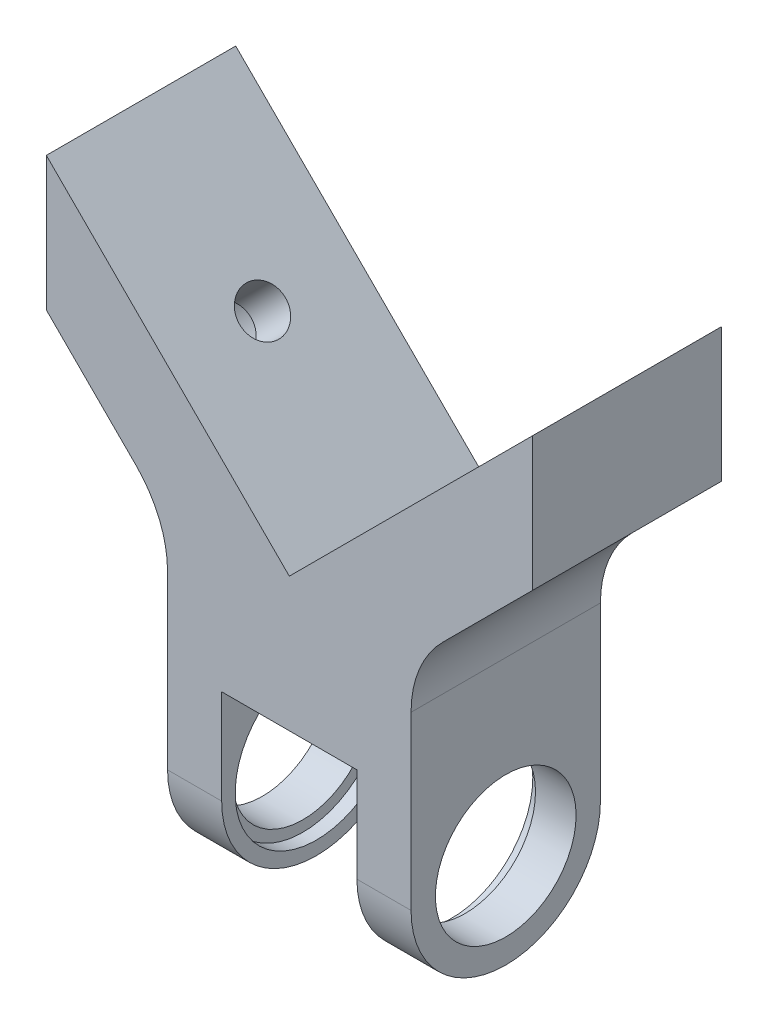
SolidWorks part; units mm, degrees
ref_plane "Alzado" through (0, 0, 0) normal (0, 0, 1) x (1, 0, 0)
ref_plane "Planta" through (0, 0, 0) normal (0, 1, 0) x (1, 0, 0)
ref_plane "Vista lateral" through (0, 0, 0) normal (1, 0, 0) x (0, 0, -1)
sketch "Croquis1" plane through (0, 0, 0) normal (1, 0, 0) x (0, 0, -1)
  line L0 (-7, 0) -> (-7, 7)
  line L1 (-7, 7) -> (7, 7)
  line L2 (7, 7) -> (7, 0)
  circle A0 centre (0, 0) radius 5.2
  circle A1 centre (0, 0) radius 6
  circle A2 centre (0, 0) radius 7
  dimension "D1" = 10.4
  dimension "D2" = 12
  dimension "D3" = 14
extrude "Saliente-Extruir1" add sketch "Croquis1" against normal blind 3 from offset 9 contours A1 A0 region at (0, 0, 5.8303)
extrude "Saliente-Extruir2" add sketch "Croquis1<3>" against normal blind 4 from offset 9 contours A2 L1 L0 | A2 L2 L1 | A2 A1 region at (0, 4.8097, 4.8097) region at (0, 5.4364, 5.4364) region at (0, 5.4364, -5.4364)
sketch "Croquis1<3>" plane through (0, 0, 0) normal (1, 0, 0) x (0, 0, -1) same geometry as "Croquis1"
extrude "Saliente-Extruir3" add sketch "Croquis1<4>" along normal blind 4 from offset 9 separate body contours A2 L1 L0 | A2 L2 L1 | A2 A1 region at (0, 4.8097, 4.8097) region at (0, 5.4364, 5.4364) region at (0, 5.4364, -5.4364) offset against normal yes
sketch "Croquis1<4>" plane through (0, 0, 0) normal (1, 0, 0) x (0, 0, -1) same geometry as "Croquis1"
extrude "Saliente-Extruir4" add sketch "Croquis1<5>" along normal blind 3 from offset 9 contours A1 A0 region at (0, 0, 5.8303) offset against normal yes
sketch "Croquis1<5>" plane through (0, 0, 0) normal (1, 0, 0) x (0, 0, -1) same geometry as "Croquis1"
sketch "Croquis2" plane through (0, 0, 0) normal (0, 0, 1) x (1, 0, 0)
  line L0 (-5, 7) -> (0, 7) construction
  line L1 (0, 7) -> (0, 0) construction
  line L2 (0, 7) -> (0, 16.8995)
  line L3 (0, 16.8995) -> (17.9605, 34.86)
  line L4 (17.9605, 34.86) -> (22.9103, 29.9103)
  line L5 (22.9103, 29.9103) -> (0, 7)
  line L6 (0, 7) -> (5, 7) construction
  line L7 (5, 0) -> (5, 7) construction
  line L8 (8.9803, 25.8798) -> (13.93, 20.93) construction
  line L9 (9, 7) -> (9, 16)
  line L10 (-9, 7) -> (9, 7)
  line L11 (0, 16.8995) -> (-17.9605, 34.86)
  line L12 (-17.9605, 34.86) -> (-22.9103, 29.9103)
  line L13 (-22.9103, 29.9103) -> (0, 7)
  line L14 (-9, 7) -> (-9, 16)
  line L15 (-17.9605, 34.86) -> (-17.9605, 24.9605)
  line L16 (17.9605, 34.86) -> (17.9605, 24.9605)
  dimension "D1" = 45
  dimension "D2" = 7
  dimension "D3" = 25.4
extrude "Saliente-Extruir5" add sketch "Croquis2" along normal blind 7 and the other way blind 7 contours L12 L13 L2 L11 | L5 L4 L3 L2 | L5 L10 L9 | L14 L10 L13 region at (-8.9803, 20.93, 0) region at (8.9803, 20.93, 0) region at (6, 10, 0) region at (-6, 10, 0)
ref_plane "Plano1" through (8.4497, 8.4497, 0) normal (0.7071, 0.7071, 0) x (0.7071, -0.7071, 0)
sketch "Croquis3" plane through (8.4497, 8.4497, 0) normal (0.7071, 0.7071, 0) x (0.7071, -0.7071, 0)
  line L0 (-24.6497, 7) -> (-24.6497, -7) construction
  line L2 (-11.9497, 7) -> (-37.3497, 7) construction
  line L3 (-11.9497, -7) -> (-37.3497, -7) construction
  circle A1 centre (-24.6497, 0) radius 1.7
  dimension "D1" = 3.4
extrude "Cortar-Extruir1" cut sketch "Croquis3" against normal up to surface (7 mm away) up to face at (-13.4803, 20.4803, 0)
ref_plane "Plano2" through (-8.4497, 8.4497, 0) normal (-0.7071, 0.7071, 0) x (0.7071, 0.7071, 0)
sketch "Croquis4" plane through (-8.4497, 8.4497, 0) normal (-0.7071, 0.7071, 0) x (0.7071, 0.7071, 0)
  line L0 (24.6497, 7) -> (24.6497, -7) construction
  line L1 (11.9497, 7) -> (37.3497, 7) construction
  line L2 (11.9497, -7) -> (37.3497, -7) construction
  circle A0 centre (24.6497, 0) radius 1.7
  dimension "D1" = 3.4
extrude "Cortar-Extruir2" cut sketch "Croquis4" against normal up to surface (7 mm away) up to face at (13.4803, 20.4803, 0)
ref_plane "Plano3" through (-3.5, 3.5, 0) normal (0.7071, -0.7071, 0) x (-0.7071, -0.7071, 0)
sketch "Croquis5" plane through (-3.5, 3.5, 0) normal (0.7071, -0.7071, 0) x (-0.7071, -0.7071, 0)
  circle A0 centre (-24.6497, 0) radius 3.2
  dimension "D1" = 6.4
extrude "Cortar-Extruir3" cut sketch "Croquis5" against normal blind 3.4
ref_plane "Plano4" through (3.5, 3.5, 0) normal (-0.7071, -0.7071, 0) x (-0.7071, 0.7071, 0)
sketch "Croquis6" plane through (3.5, 3.5, 0) normal (-0.7071, -0.7071, 0) x (-0.7071, 0.7071, 0)
  circle A0 centre (24.6497, 0) radius 3.2
  dimension "D1" = 6.4
extrude "Cortar-Extruir4" cut sketch "Croquis6" against normal blind 3.4
fillet "Redondeo1" radius 8 2 edges at (9, 16, 0) (-9, 16, 0)
